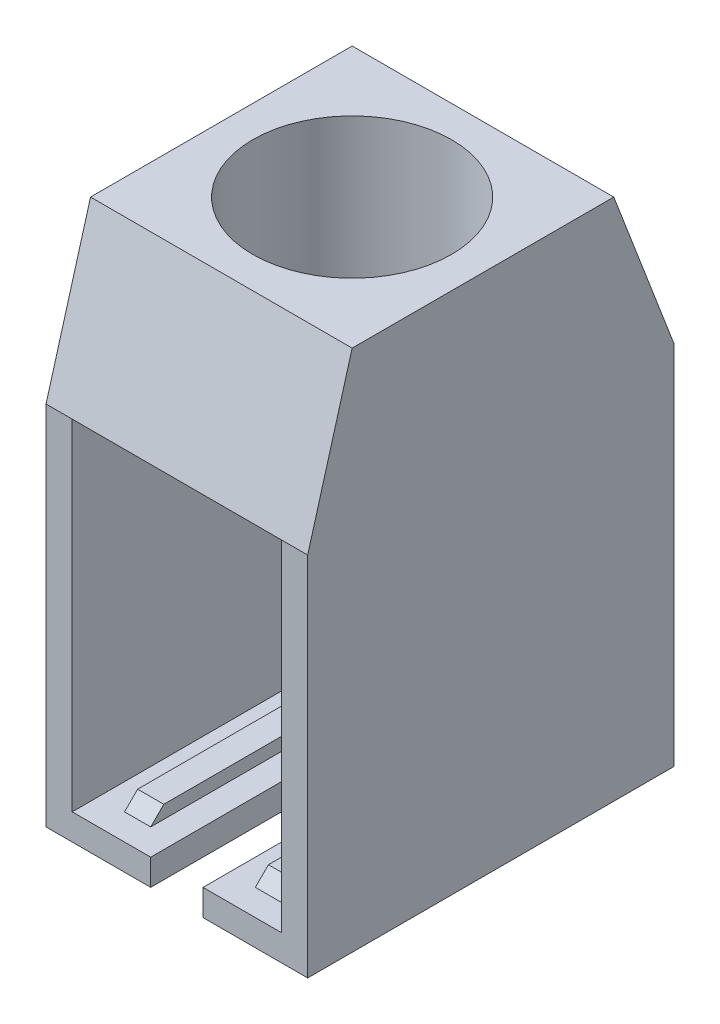
SolidWorks part; units mm, degrees
material "PVC 0.007 Plasticized"
ref_plane "Front Plane" through (0, 0, 0) normal (0, 0, 1) x (1, 0, 0)
ref_plane "Top Plane" through (0, 0, 0) normal (0, 1, 0) x (1, 0, 0)
ref_plane "Right Plane" through (0, 0, 0) normal (1, 0, 0) x (0, 0, -1)
sketch "Sketch1" plane through (0, 0, 0) normal (0, 1, 0) x (1, 0, 0)
  line L1 (2.5, 3.5) -> (-2.5, 3.5)
  line L2 (2.5, 3.5) -> (2.5, -3.5)
  line L3 (2.5, -3.5) -> (-2.5, -3.5)
  line L4 (-2.5, 3.5) -> (-2.5, -3.5)
  line L5 (2.5, 3.5) -> (-2.5, -3.5) construction
  line L6 (2.5, -3.5) -> (-2.5, 3.5) construction
  point P0 (0, 0)
  dimension "D1" = 5
  dimension "D2" = 7
extrude "Boss-Extrude1" add sketch "Sketch1" along normal blind 10
sketch "Sketch2" plane through (2.5, 0, 0) normal (1, 0, 0) x (0, 0, -1)
  line L0 (-3.5, 7) -> (-2.65, 10)
  line L1 (-3.5, 10) -> (-3.5, 0) construction
  line L2 (-3.5, 10) -> (3.5, 10) construction
  line L3 (-2.65, 10) -> (-3.5, 10)
  line L4 (-3.5, 10) -> (-3.5, 7)
  line L5 (2.35, 10) -> (3.5, 10)
  line L6 (3.5, 10) -> (3.5, 7)
  line L7 (3.5, 10) -> (3.5, 0) construction
  line L8 (3.5, 7) -> (2.35, 10)
  line L9 (-0.15, 10) -> (-0.15, 0) construction
  line L10 (-3.5, 0) -> (3.5, 0) construction
  line L11 (-2.65, 10) -> (2.35, 10) construction
  point P11 (-0.15, 10)
  dimension "D1" = 7
  dimension "D2" = 5
  dimension "D3" = 3.35
extrude "Cut-Extrude1" cut sketch "Sketch2" against normal through all
sketch "Sketch3" plane through (0, 0, 3.5) normal (0, 0, 1) x (1, 0, 0)
  line L0 (2.5, 7) -> (2.5, 0) construction
  line L1 (-2, 6.5) -> (2, 6.5)
  line L2 (-2, 6.5) -> (-2, 0.5)
  line L3 (-2, 0.5) -> (2, 0.5)
  line L4 (2, 6.5) -> (2, 0.5)
  line L5 (-2, 6.5) -> (2, 0.5) construction
  line L6 (-2, 0.5) -> (2, 6.5) construction
  line L7 (-2.5, 0) -> (2.5, 0) construction
  line L9 (-2.5, 7) -> (2.5, 7) construction
  point P0 (0, 3.5)
  dimension "D1" = 0.5
  dimension "D2" = 0.5
  dimension "D3" = 0.5
extrude "Cut-Extrude2" cut sketch "Sketch3" against normal offset from surface (6.5 mm away) 0.5 up to face at (0, 3.5, -3.5)
sketch "Sketch4" plane through (0, 10, 0) normal (0, 1, 0) x (1, 0, 0)
  circle A0 centre (0, -0.15) radius 1.9
  point P2 (2.5, -0.15)
  dimension "D1" = 3.8
extrude "Cut-Extrude3" cut sketch "Sketch4" against normal up to next
sketch "Sketch5" plane through (0, 0, 0) normal (0, -1, 0) x (1, 0, 0)
  line L0 (-0.5, 3.5) -> (-0.5, 0.15)
  line L1 (-2.5, 3.5) -> (2.5, 3.5) construction
  line L2 (0.5, 0.15) -> (0.5, 3.5)
  line L3 (0.5, 3.5) -> (-0.5, 3.5)
  circle A0 centre (0, 0.15) radius 1.9 construction
  circle A1 centre (0, 0.15) radius 1.9 construction
  arc A2 (-0.5, 0.15) -> (0.5, 0.15) centre (0, 0.15) ccw
  point P10 (0, 3.5)
  dimension "D1" = 1
extrude "Cut-Extrude4" cut sketch "Sketch5" against normal up to next
sketch "Sketch6" plane through (0, 0.5, 0) normal (0, 1, 0) x (1, 0, 0)
  line L0 (-2, 0) -> (-1.25, 0)
  line L1 (-1.5, 3) -> (-1, 3)
  line L2 (-1.5, 3) -> (-1.5, -3)
  line L3 (-1.5, -3) -> (-1, -3)
  line L4 (-1, 3) -> (-1, -3)
  line L5 (-1.5, 3) -> (-1, -3) construction
  line L6 (-1.5, -3) -> (-1, 3) construction
  line L7 (1, 3) -> (1.5, 3)
  line L8 (1, 3) -> (1, -3)
  line L9 (1, -3) -> (1.5, -3)
  line L10 (1.5, 3) -> (1.5, -3)
  line L11 (1, 3) -> (1.5, -3) construction
  line L12 (1, -3) -> (1.5, 3) construction
  line L13 (-1.25, 0) -> (-1, 0)
  line L14 (1.25, 0) -> (2, 0)
  line L19 (0.5, -0.15) -> (0.5, -3.5)
  line L20 (0.5, -3.5) -> (2, -3.5)
  line L21 (2, -3.5) -> (2, 3)
  line L22 (2, 3) -> (-2, 3)
  line L23 (-2, 3) -> (-2, -3.5)
  line L24 (-2, -3.5) -> (-0.5, -3.5)
  line L25 (-0.5, -3.5) -> (-0.5, -0.15)
  line L26 (0.5, -0.15) -> (0.5, -3.5) construction
  line L27 (0.5, -3.5) -> (2, -3.5) construction
  line L28 (2, -3.5) -> (2, 3) construction
  line L29 (2, 3) -> (-2, 3) construction
  line L30 (-2, 3) -> (-2, -3.5) construction
  line L31 (-2, -3.5) -> (-0.5, -3.5) construction
  line L32 (-0.5, -3.5) -> (-0.5, -0.15) construction
  arc A1 (0.5, -0.15) -> (-0.5, -0.15) centre (0, -0.15) ccw
  arc A2 (0.5, -0.15) -> (-0.5, -0.15) centre (0, -0.15) ccw construction
  point P0 (-1.25, 0)
  point P5 (1.25, 0)
  point P26 (-1.25, -3)
  point P27 (-1.25, -3.5)
  point P29 (1.25, -3.5)
  dimension "D1" = 0
  dimension "D2" = 0.5
extrude "Boss-Extrude3" add sketch "Sketch6" along normal blind 0.25
chamfer "Chamfer1" distance 0.25 angle 45 2 edges at (1.25, 0.75, 3) (-1.25, 0.75, 3)
chamfer "Chamfer2" distance 0.5 angle 45 1 edges at (0, 6.5, 3.5)
equation "\"Pin Spacing\"= 5mm"
equation "\"Connector Height\"= 10mm"
equation "\"Connector Depth\"= 7mm"
equation "\"Connector Width\"= \"Pin Spacing\""
equation "\"D1@Sketch1\"=\"Connector Width\""
equation "\"D2@Sketch1\"=\"Connector Depth\""
equation "\"D1@Boss-Extrude1\"=\"Connector Height\""
equation "\"Set Screw Diameter\"= 3.5mm"
equation "\"D1@Sketch4\"=\"Set Screw Diameter\" +.3"
equation "\"Pin Width\"= .9mm"
